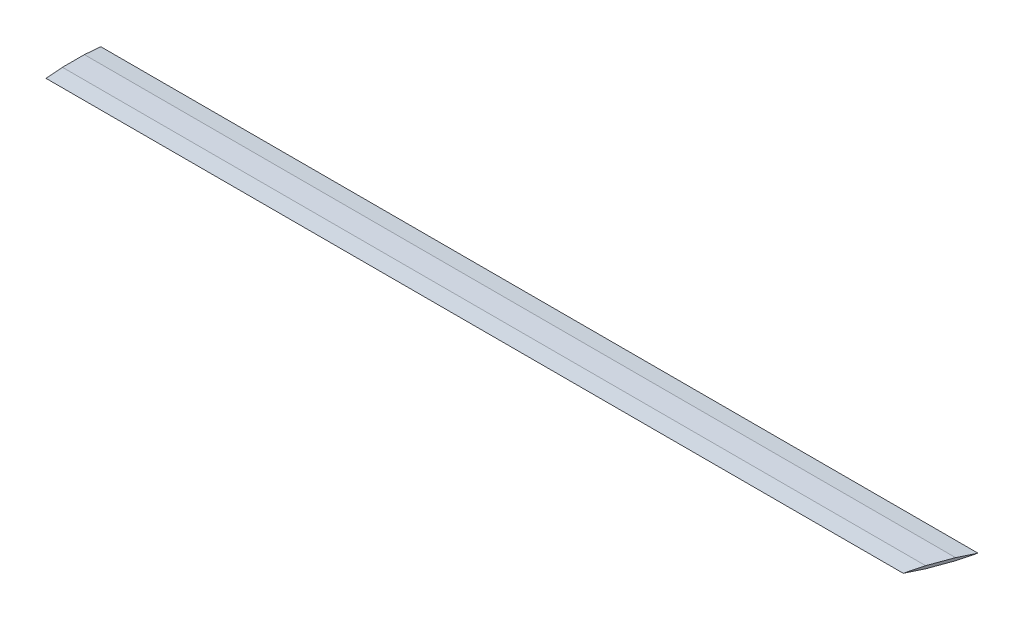
SolidWorks part; units mm, degrees
ref_plane "Front Plane" through (0, 0, 0) normal (0, 0, 1) x (1, 0, 0)
ref_plane "Top Plane" through (0, 0, 0) normal (0, 1, 0) x (1, 0, 0)
ref_plane "Right Plane" through (0, 0, 0) normal (1, 0, 0) x (0, 0, -1)
sketch "Sketch1" plane through (0, 0, 0) normal (0, 1, 0) x (1, 0, 0)
  line L0 (0, 0) -> (320, 0)
  line L1 (320, 0) -> (312.7206, -20)
  line L2 (312.7206, -20) -> (0, -20)
  line L3 (0, -20) -> (0, 0)
  point P2 (234.8343, -6.4107)
  point P5 (0, 0)
  point P7 (0, -25)
  dimension "D1" = 20
  dimension "D2" = 320
  dimension "D4" = 110
  dimension "D5" = 20
extrude "Boss-Extrude1" add sketch "Sketch1" along normal blind 1 contours L3 L2 L1 L0 region at (158.1871, 0, 9.9617)
chamfer "Chamfer1" distance 6 distance2 0.5 2 edges at (160, 0, 0) (160, 1, 0) first distance on face at (158.1801, 0, 10) first distance on face at (158.1801, 1, 10)
chamfer "Chamfer2" distance 6 distance2 0.5 2 edges at (156.3603, 0, 20) (156.3603, 1, 20) first distance on face at (157.6342, 0, 13) first distance on face at (157.6342, 1, 13)
